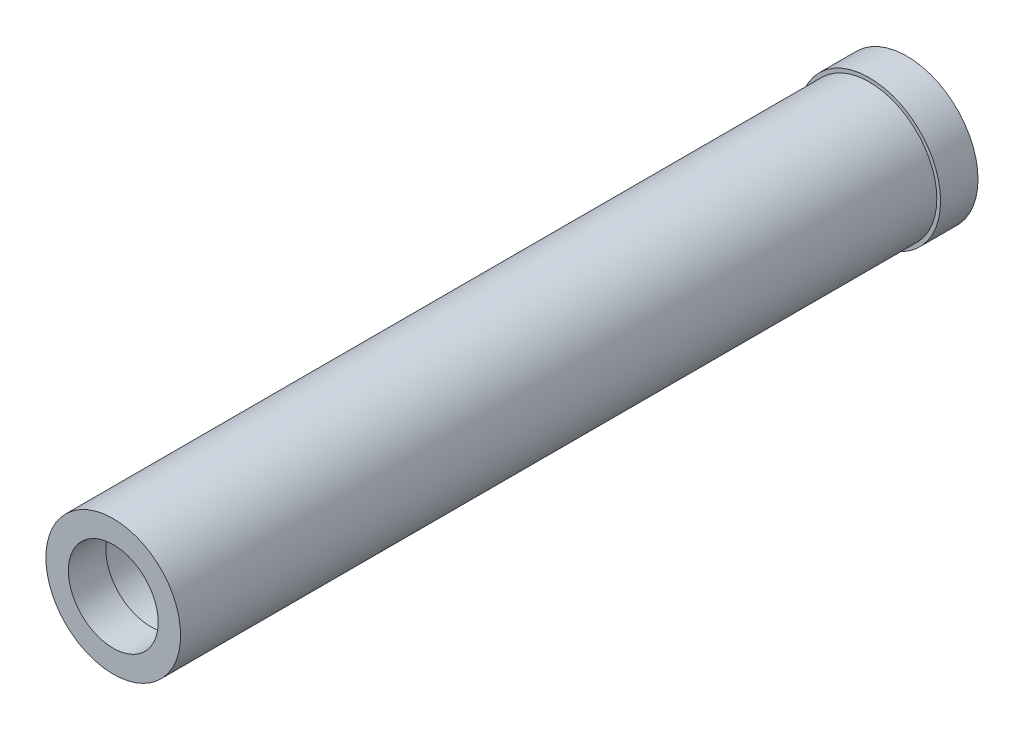
SolidWorks part; units mm, degrees
ref_plane "Front Plane" through (0, 0, 0) normal (0, 0, 1) x (1, 0, 0)
ref_plane "Top Plane" through (0, 0, 0) normal (0, 1, 0) x (1, 0, 0)
ref_plane "Right Plane" through (0, 0, 0) normal (1, 0, 0) x (0, 0, -1)
sketch "Sketch1" plane through (0, 0, 0) normal (0, 0, 1) x (1, 0, 0)
  circle A0 centre (0, 0) radius 19
  circle A1 centre (0, 0) radius 18
  dimension "D1" = 38
  dimension "D2" = 36
extrude "Boss-Extrude1" add sketch "Sketch1" along normal blind 10 contours A1 | A0 A1 region at (-18.4626, 0, 0) region at (0, 0, 0)
extrude "Boss-Extrude2" add sketch "Sketch1<3>" along normal blind 212 contours A1 region at (0, 0, 0)
sketch "Sketch1<3>" plane through (0, 0, 0) normal (0, 0, 1) x (1, 0, 0) same geometry as "Sketch1"
sketch "Sketch2" plane through (0, 0, 212) normal (0, 0, 1) x (1, 0, 0)
  circle A0 centre (0, 0) radius 13
  dimension "D1" = 26
extrude "Cut-Extrude1" cut sketch "Sketch2" against normal blind 200
sketch "Sketch3" plane through (0, 0, 212) normal (0, 0, 1) x (1, 0, 0)
  circle A0 centre (0, 0) radius 13
  circle A1 centre (0, 0) radius 12
  dimension "D1" = 24
extrude "Boss-Extrude3" add sketch "Sketch3" against normal blind 10
